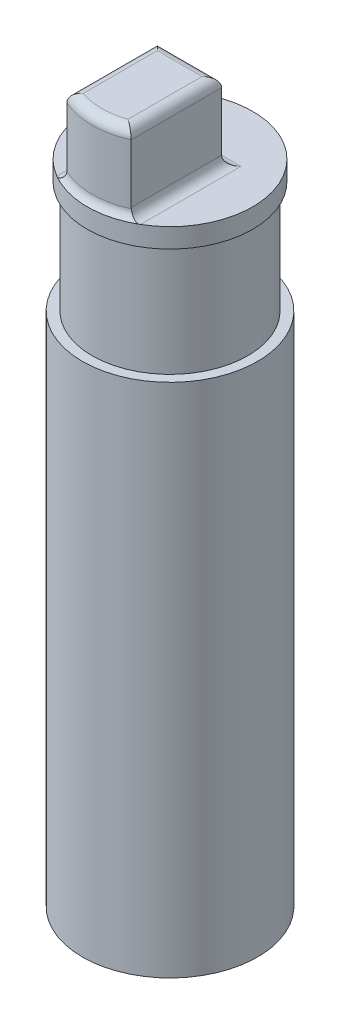
SolidWorks part; units mm, degrees
ref_plane "Alzado" through (0, 0, 0) normal (0, 0, 1) x (1, 0, 0)
ref_plane "Planta" through (0, 0, 0) normal (0, 1, 0) x (1, 0, 0)
ref_plane "Vista lateral" through (0, 0, 0) normal (1, 0, 0) x (0, 0, -1)
sketch "Croquis1" plane through (0, 0, 0) normal (0, 1, 0) x (1, 0, 0)
  circle A0 centre (0, 0) radius 9
  dimension "D1" = 18
extrude "Saliente-Extruir1" add sketch "Croquis1" along normal blind 53
sketch "Croquis2" plane through (0, 53, 0) normal (0, 1, 0) x (1, 0, 0)
  circle A0 centre (0, 0) radius 8
  dimension "D1" = 16
extrude "Saliente-Extruir2" add sketch "Croquis2" along normal blind 11.5
sketch "Croquis3" plane through (0, 64.5, 0) normal (0, 1, 0) x (1, 0, 0)
  circle A0 centre (0, 0) radius 8.5
  dimension "D1" = 17
extrude "Saliente-Extruir3" add sketch "Croquis3" along normal blind 2
sketch "Croquis4" plane through (0, 66.5, 0) normal (0, 1, 0) x (1, 0, 0)
  line L0 (-8.5, 0) -> (8.5, 0) construction
  line L1 (0, -8.5) -> (0, 8.5) construction
  line L2 (-3.3, -7.2877) -> (-3.3, 2)
  line L3 (3.3, -7.2877) -> (3.3, 2)
  line L6 (-3.3, 2) -> (3.3, 2)
  line L9 (-3.3, -8.5) -> (-3.3, 8.5) construction
  line L11 (3.3, -8.5) -> (3.3, 8.5) construction
  circle A0 centre (0, 0) radius 8.5 construction
  arc A1 (-3.3, -7.2877) -> (3.3, -7.2877) centre (0, 0) ccw
extrude "Saliente-Extruir4" add sketch "Croquis4" along normal blind 8
fillet "Redondeo1" radius 1 4 edges at (3.3, 66.5, 2.6438) (0, 66.5, -2) (-3.3, 66.5, 2.6438) (0, 66.5, 8)
fillet "Redondeo2" radius 1 4 edges at (0, 74.5, -2) (-3.3, 74.5, 2.6438) (0, 74.5, 8) (3.3, 74.5, 2.6438)
